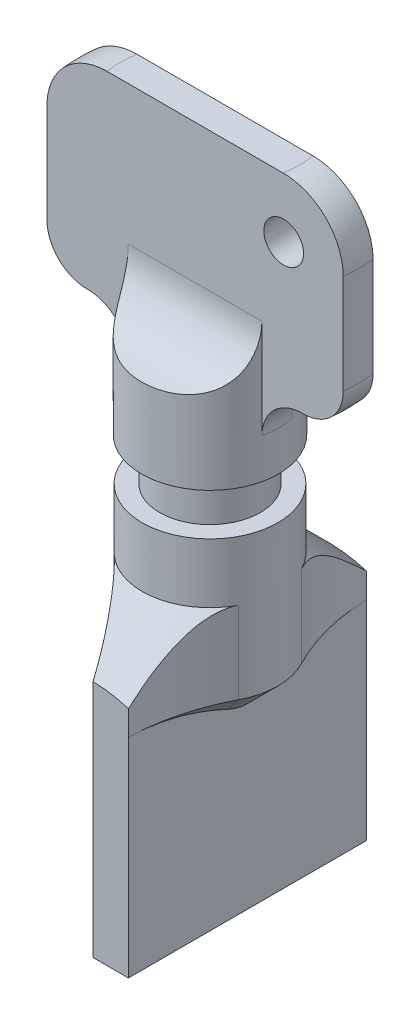
SolidWorks part; units mm, degrees
ref_plane "Front Plane" through (0, 0, 0) normal (0, 0, 1) x (1, 0, 0)
ref_plane "Top Plane" through (0, 0, 0) normal (0, 1, 0) x (1, 0, 0)
ref_plane "Right Plane" through (0, 0, 0) normal (1, 0, 0) x (0, 0, -1)
sketch "Sketch1" plane through (0, 0, 0) normal (0, 0, 1) x (1, 0, 0)
  line L0 (-3.4489, 37.7658) -> (-3.4489, 33.7658)
  line L1 (-3.4489, 33.7658) -> (-2.5348, 33.7658)
  line L2 (-2.5348, 33.7658) -> (-2.5348, 31.625)
  line L3 (-2.5348, 31.625) -> (-3.4177, 31.625)
  line L4 (-3.4177, 31.625) -> (-3.4177, 23)
  line L5 (-3.4177, 23) -> (0, 23)
  line L6 (-3.4489, 37.7658) -> (0, 37.7658)
  line L7 (0, 37.7658) -> (0, 23)
  dimension "D1" = 33.7658
  dimension "D2" = 2.1409
  dimension "D3" = 23
  dimension "D4" = 4
revolve "Revolve1" add sketch "Sketch1" angle 360 about L7
sketch "Sketch2" plane through (0, 37.7658, 0) normal (0, 1, 0) x (1, 0, 0)
  line L1 (-11.4046, 0.75) -> (11.4046, 0.75)
  line L2 (-11.4046, 0.75) -> (-11.4046, -0.75)
  line L3 (-11.4046, -0.75) -> (11.4046, -0.75)
  line L4 (11.4046, 0.75) -> (11.4046, -0.75)
  line L5 (-11.4046, 0.75) -> (11.4046, -0.75) construction
  line L6 (-11.4046, -0.75) -> (11.4046, 0.75) construction
  circle A0 centre (0, 0) radius 3.4489
  circle A1 centre (0, 0) radius 7.5
  circle M3 centre (0, 0) radius 3.4489
  dimension "D2" = 15
  dimension "D1" = 1.5
extrude "Boss-Extrude1" add sketch "Sketch2" along normal blind 10 contours L3 L1 M3 | L1 A1 L3 M3 | L3 A1 L1 M3 region at (-5.4544, 37.7658, 0) region at (0, 37.7658, 0) region at (5.4544, 37.7658, 0)
fillet "Fillet2" radius 2 4 edges at (7.5, 37.7658, 0) (-7.5, 37.7658, 0) (-3.4489, 37.7658, 0) (3.4489, 37.7658, 0)
fillet "Fillet3" radius 3 4 edges at (-7.5, 47.7658, 0) (7.5, 47.7658, 0) (0, 37.7658, -0.75) (0, 37.7658, 0.75)
sketch "Sketch3" plane through (0, 0, 0) normal (0, 0, 1) x (1, 0, 0)
  line L0 (-4.4371, 47.7658) -> (4.4371, 47.7658) construction
  line L1 (7.4624, 44.7658) -> (7.4624, 39.7658) construction
  circle A0 centre (4.4624, 44.7658) radius 1
  dimension "D1" = 2
  dimension "D2" = 3
  dimension "D3" = 3
extrude "Cut-Extrude1" cut sketch "Sketch3" against normal through all and the other way through all
sketch "Sketch4" plane through (0, 0, 0) normal (0, 0, 1) x (1, 0, 0)
  line L0 (0.11, 25.6253) -> (1.89, 14) construction
  line L1 (0.11, 25.6253) -> (1.89, 25.6253)
  line L2 (0.11, 25.6253) -> (0.11, 14)
  line L3 (0.11, 14) -> (1.89, 14)
  line L4 (1.89, 25.6253) -> (1.89, 14)
  line L5 (1.89, 25.6253) -> (0.11, 14) construction
  point P4 (1, 19.8127)
  dimension "D1" = 1.78
  dimension "D2" = 1
  dimension "D3" = 14
  dimension "D4" = 1.78
extrude "Boss-Extrude2" add sketch "Sketch4" along normal blind 6 and the other way blind 6
chamfer "Chamfer1" distance 3 angle 45 2 edges at (1.0396, 25.6253, -3.2557) (1.0396, 25.6253, 3.2557)
fillet "Fillet4" radius 10 4 edges at (0.11, 25.8127, -3.4159) (0.11, 25.8127, 3.4159) (1.89, 25.8127, -2.8475) (1.89, 25.8127, 2.8475)
chamfer "Chamfer2" distance 1.5 angle 45 6 edges at (-0.9189, 23, -4.1218) (-0.9189, 23, 4.1218) (-3.4177, 23, 0) (2.204, 23, 3.7268) (2.204, 23, -3.7268) (3.4177, 23, 0)
